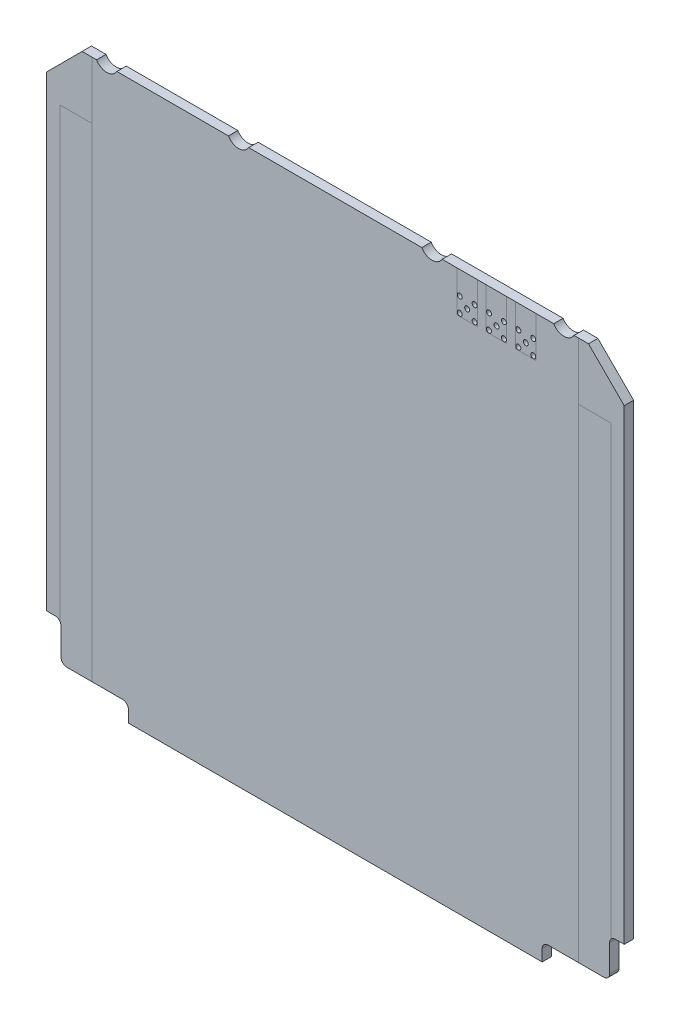
SolidWorks part; units mm, degrees
material "FR4_stuffedProtoboard"
ref_plane "Front Plane" through (0, 0, 0) normal (0, 0, 1) x (1, 0, 0)
ref_plane "Top Plane" through (0, 0, 0) normal (0, 1, 0) x (1, 0, 0)
ref_plane "Right Plane" through (0, 0, 0) normal (1, 0, 0) x (0, 0, -1)
ref_plane "Plane4" through (0, 0, -0.0125) normal (0, 0, -1) x (-1, 0, 0)
sketch "Sketch1" plane through (0, 0, -0.0125) normal (0, 0, -1) x (-1, 0, 0)
  line L4 (49.3, -50) -> (49.3, 45.3)
  line L6 (49.3, 45.3) -> (-49.3, 45.3)
  line L12 (-49.3, 45.3) -> (-49.3, -50)
  line L17 (-49.3, -50) -> (49.3, -50)
  line L18 (0, -50) -> (0, 45.3) construction
  point P1 (0, 0)
  point P2 (0, 0)
  point P3 (0, 0)
  point P11 (0, 0)
  point P13 (0, 0)
  point P14 (0, 0)
  point P15 (10.2945, 45.3)
  point P16 (0, 0)
  dimension "D7" = 95.3
  dimension "D1" = 98.6
  dimension "D34" = 50
extrude "basicSize" add sketch "Sketch1" against normal blind 1.6
chamfer "Chamfer1" distance 6.1 angle 45 2 edges at (49.3, 45.3, 0.7875) (-49.3, 45.3, 0.7875)
sketch "Sketch4" plane through (0, 0, 1.5875) normal (0, 0, 1) x (1, 0, 0)
  line L1 (37.2679, 45.3) -> (40.7321, 45.3)
  line L7 (-43.2, 45.3) -> (43.2, 45.3) construction
  line L8 (49.3, 39.2) -> (49.3, -50) construction
  arc A0 (40.7321, 45.3) -> (37.2679, 45.3) centre (39, 46.3) cw
  point P5 (39, 44.3)
  point P6 (0, 0)
  point P16 (0, 0)
  dimension "D1" = 2
  dimension "D3" = 10.3
  dimension "D2" = 1
extrude "backplaneSideScrewCutout" cut sketch "Sketch4" against normal through all both and the other way through all
pattern_linear "LPattern3" count 2 spacing 22.5 along (-1, 0, 0) of "backplaneSideScrewCutout"
mirror "Mirror3" about plane through (0, 0, 0) normal (1, 0, 0) of "LPattern3"
sketch "Sketch6" plane through (0, 0, 1.5875) normal (0, 0, 1) x (1, 0, 0)
  line L0 (-49.3, -50) -> (-49.3, 39.2) construction
  line L1 (-49.3, -40.4) -> (-46.8, -40.4)
  line L2 (-49.3, -40.4) -> (-49.3, -50)
  line L4 (-46.8, -40.4) -> (-46.8, -47)
  line L5 (49.3, -50) -> (-49.3, -50) construction
  line L6 (-35.3, -50) -> (-49.3, -50)
  line L7 (-35.3, -50) -> (-35.3, -47)
  line L8 (-35.3, -47) -> (-46.8, -47)
  dimension "D1" = 2.5
  dimension "D2" = 3
  dimension "D3" = 9.6
  dimension "D4" = 14
extrude "Cut-Extrude4" cut sketch "Sketch6" against normal through all
fillet "Fillet1" radius 1 3 edges at (-35.3, -47, 0.7875) (-46.8, -47, 0.7875) (-46.8, -40.4, 0.7875)
mirror "Mirror1" about plane through (0, 0, 0) normal (1, 0, 0) of "Cut-Extrude4", "Fillet1"
sketch "Sketch5" plane through (0, 0, 1.5875) normal (0, 0, 1) x (1, 0, 0)
  line L0 (21.23, 41.37) -> (23.77, 38.83) construction
  line L1 (21.23, 38.83) -> (21.23, 41.37) construction
  line L2 (21.23, 41.37) -> (23.77, 41.37) construction
  line L4 (49.3, 39.2) -> (49.3, -40.4) construction
  line L5 (-14.7679, 45.3) -> (14.7679, 45.3) construction
  circle A0 centre (22.5, 40.1) radius 0.425
  circle A1 centre (21.23, 41.37) radius 0.425
  circle A3 centre (21.23, 38.83) radius 0.425
  circle A4 centre (23.77, 41.37) radius 0.425
  circle A5 centre (23.77, 38.83) radius 0.425
  point P6 (15.3087, 34.0739)
  point P15 (0, 0)
  dimension "D2" = 0.85
  dimension "D1" = 2.54
  dimension "D3" = 3.93
  dimension "D4" = 28.07
extrude "Cut-Extrude3" cut sketch "Sketch5" against normal through all
pattern_linear "LPattern2" count 3 spacing 5 along (1, 0, 0) of "Cut-Extrude3"
sketch "partFootprints" plane through (0, 0, 1.5875) normal (0, 0, 1) x (1, 0, 0)
  line L1 (18.2321, 45.3) -> (37.2679, 45.3) construction
  line L6 (20.75, 45.3) -> (20.75, 38.35)
  line L7 (20.75, 38.35) -> (24.25, 38.35)
  line L8 (24.25, 38.35) -> (24.25, 45.3)
  line L9 (24.25, 45.3) -> (20.75, 45.3)
  line L10 (25.75, 45.3) -> (25.75, 38.35)
  line L11 (25.75, 38.35) -> (29.25, 38.35)
  line L12 (29.25, 38.35) -> (29.25, 45.3)
  line L13 (29.25, 45.3) -> (25.75, 45.3)
  line L14 (30.75, 45.3) -> (30.75, 38.35)
  line L15 (30.75, 38.35) -> (34.25, 38.35)
  line L16 (34.25, 38.35) -> (34.25, 45.3)
  line L17 (34.25, 45.3) -> (30.75, 45.3)
  line L19 (32.5, 38.35) -> (32.5, 40.1) construction
  line L23 (22.5, 38.35) -> (22.5, 40.1) construction
  circle A2 centre (22.5, 40.1) radius 0.425 construction
  circle A5 centre (32.5, 40.1) radius 0.425 construction
  point P0 (34.25, 45.3)
  dimension "D1" = 1.75
  dimension "D8" = 3.5
  dimension "D6" = 3
extrude "footPrints" cut sketch "partFootprints" against normal blind 0.0001
sketch "thermalContacts_upper" plane through (0, 0, 1.5875) normal (0, 0, 1) x (1, 0, 0)
  line L0 (-49.3, -40.4) -> (-49.3, 39.2) construction
  line L1 (35.3, -50) -> (-35.3, -50) construction
  line L2 (-49.3, 45.3) -> (49.3, 45.3) construction
  line L3 (-47, 35.5) -> (-47, -41.5)
  line L5 (-41.5, 35.5) -> (-47, 35.5)
  line L18 (-41.5, 35.5) -> (-41.5, 47)
  line L23 (-41.5, 47) -> (-56.1922, 47)
  line L24 (-56.1922, 47) -> (-56.1922, -41.5)
  line L25 (-56.1922, -41.5) -> (-47, -41.5)
  point P10 (-41.5, 35.7705)
  dimension "D1" = 2.3
  dimension "D2" = 8.5
  dimension "D3" = 9.8
  dimension "D4" = 7.8
  dimension "D5" = 88.5
  dimension "D6" = 14.6922
extrude "keepOut_bottom" cut sketch "thermalContacts_upper" against normal blind 0.0001
sketch "Sketch3" plane through (0, 0, 1.5875) normal (0, 0, 1) x (1, 0, 0)
  line L0 (18.2321, 45.3) -> (20.75, 45.3) construction
  line L1 (-46.8, -46) -> (-46.8, -41.4) construction
  line L2 (-36.3, -47) -> (-45.8, -47) construction
  line L3 (-47, -40.8) -> (-47, 35.5) construction
  line L10 (0, -50) -> (0, 45.3) construction
  line L11 (35.3, -50) -> (-35.3, -50) construction
  line L13 (-41.5, 35.5) -> (-47, 35.5)
  line L14 (-45.8, -47) -> (-41.5, -47)
  line L15 (-46.8, -41.4) -> (-46.8, -46)
  line L16 (-47, 35.5) -> (-47, -40.8)
  line L17 (-41.5, -47) -> (-41.5, 35.5)
  arc A2 (-46.8, -41.4) -> (-47, -40.8) centre (-47.8, -41.4) ccw construction
  arc A3 (-46.8, -46) -> (-45.8, -47) centre (-45.8, -46) ccw construction
  arc A4 (-45.8, -47) -> (-46.8, -46) centre (-45.8, -46) cw
  arc A5 (-47, -40.8) -> (-46.8, -41.4) centre (-47.8, -41.4) cw
  point P0 (-41.4913, 35.4618)
extrude "caution_top" cut sketch "Sketch3" against normal blind 0.0001
ref_plane "midplane_Z" through (0, 0, 0.7875) normal (0, 0, 1) x (1, 0, 0)
mirror "clearances_top-bottom" about plane through (0, 0, 0.7875) normal (0, 0, 1) of "keepOut_bottom", "caution_top"
mirror "clearances_side-side" about plane through (0, 0, 0) normal (1, 0, 0) of "clearances_top-bottom"
ref_point "rail midpoint"
